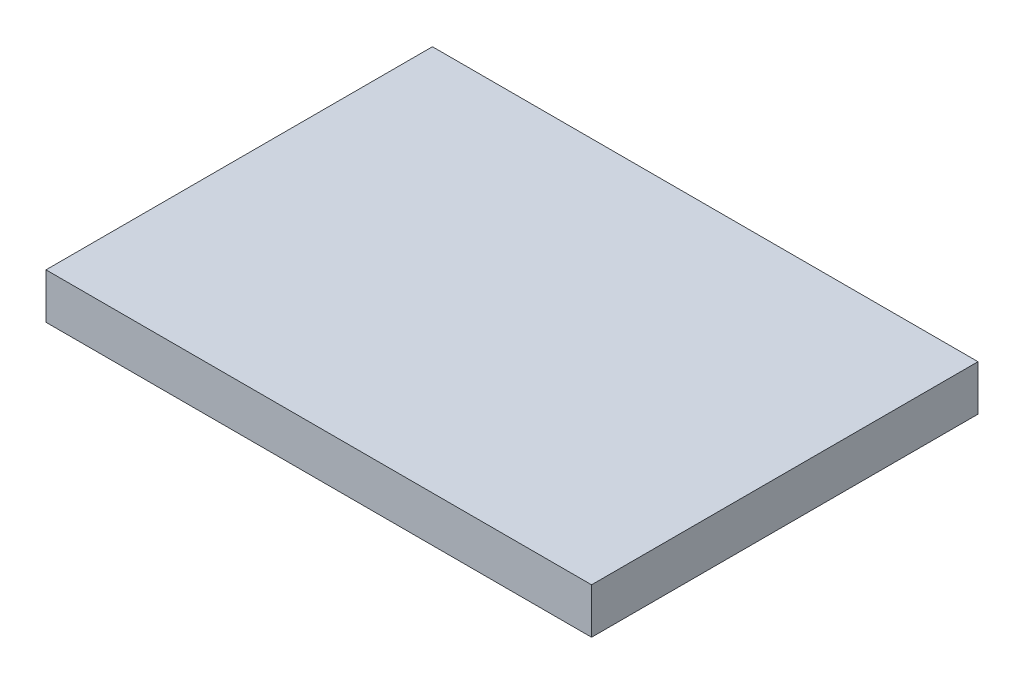
SolidWorks part; units mm, degrees
ref_plane "Front Plane" through (0, 0, 0) normal (0, 0, 1) x (1, 0, 0)
ref_plane "Top Plane" through (0, 0, 0) normal (0, 1, 0) x (1, 0, 0)
ref_plane "Right Plane" through (0, 0, 0) normal (1, 0, 0) x (0, 0, -1)
sketch "Sketch1" plane through (0, 0, 0) normal (0, 1, 0) x (1, 0, 0)
  line L1 (-12, -8.5) -> (12, -8.5)
  line L2 (-12, -8.5) -> (-12, 8.5)
  line L3 (-12, 8.5) -> (12, 8.5)
  line L4 (12, -8.5) -> (12, 8.5)
  line L5 (-12, -8.5) -> (12, 8.5) construction
  line L6 (-12, 8.5) -> (12, -8.5) construction
  point P0 (0, 0)
  dimension "D1" = 17
  dimension "D2" = 24
extrude "Boss-Extrude1" add sketch "Sketch1" along normal blind 2
